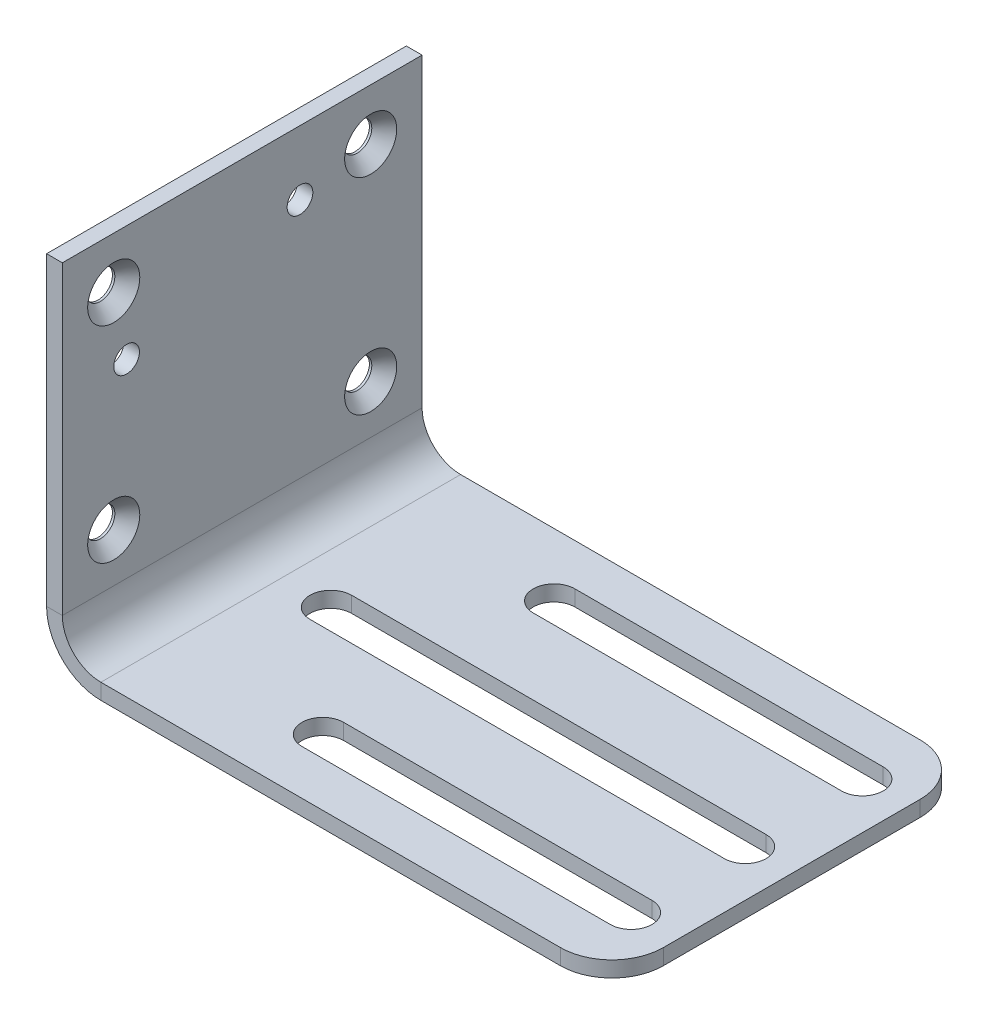
SolidWorks part; units mm, degrees
note: The reader was unsure of these and kept them because the rebuilt part matched: bend radius of "BaseBend1".
material "AISI 1095 CRS, GALV"
ref_plane "Front Plane" through (0, 0, 0) normal (0, 0, 1) x (1, 0, 0)
ref_plane "Top Plane" through (0, 0, 0) normal (0, 1, 0) x (1, 0, 0)
ref_plane "Right Plane" through (0, 0, 0) normal (1, 0, 0) x (0, 0, -1)
sketch "Sketch1" plane through (0, 0, 0) normal (0, 0, 1) x (1, 0, 0)
  line L0 (0, 0) -> (0, 88.9)
  line L1 (0, 0) -> (139.7, 0)
  dimension "D1" = 139.7
  dimension "D2" = 88.9
sheet metal parameters "Sheet-Metal1" thickness 3.8913 parameters "D1"=9.525
base flange "Base-Flange1" sketch "Sketch1" end condition mid plane depth 88.9 reverse direction no thickness 3.8913 reverse thickness direction yes bend radius 9.525
bend "BaseBend1" bend radius 9.525 bend angle 90 parameters "D5"=1
sketch "Sketch4" plane through (0, 3.8913, 0) normal (0, 1, 0) x (1, 0, 0)
  line L0 (25.781, 0) -> (128.1938, 0) construction
  line L1 (25.781, 5.1562) -> (128.1938, 5.1562)
  line L2 (25.781, -5.1562) -> (128.1938, -5.1562)
  line L3 (139.7, -44.45) -> (139.7, 44.45) construction
  line L4 (13.4163, -44.45) -> (139.7, -44.45) construction
  arc A0 (25.781, 5.1562) -> (25.781, -5.1562) centre (25.781, 0) ccw
  arc A1 (128.1938, -5.1562) -> (128.1938, 5.1562) centre (128.1938, 0) ccw
  point P2 (76.9874, 0)
  dimension "D1" = 10.3124
  dimension "D2" = 112.7252
  dimension "D3" = 62.7126
  dimension "D4" = 44.45
extrude "LONG-SLOT" cut sketch "Sketch4" against normal through all normal cut yes
sketch "Sketch5" plane through (0, 3.8913, 0) normal (0, 1, 0) x (1, 0, 0)
  line L0 (51.9938, -28.194) -> (128.1938, -28.194) construction
  line L1 (51.9938, -23.0378) -> (128.1938, -23.0378)
  line L2 (51.9938, -33.3502) -> (128.1938, -33.3502)
  line L3 (13.4163, -44.45) -> (139.7, -44.45) construction
  arc A0 (51.9938, -23.0378) -> (51.9938, -33.3502) centre (51.9938, -28.194) ccw
  arc A1 (128.1938, -33.3502) -> (128.1938, -23.0378) centre (128.1938, -28.194) ccw
  point P2 (90.0938, -28.194)
  dimension "D1" = 10.3124
  dimension "D2" = 86.5124
  dimension "D3" = 16.256
extrude "SHORT-SLOT" cut sketch "Sketch5" against normal through all normal cut yes
pattern_linear "LPattern1" count 2 spacing 57.15 along (0, 0, -1) of "SHORT-SLOT"
hole_wizard "CSK for 1/4 Flat Head Machine Screw1" positions "Sketch7" profile "Sketch6" countersink size "1/4" standard "ANSI Inch" end condition through all
sketch "Sketch7" plane through (3.8913, 0, 0) normal (1, 0, 0) x (0, 0, -1)
  line L0 (-44.45, 88.9) -> (-44.45, 13.4163) construction
  line L1 (-44.45, 88.9) -> (44.45, 88.9) construction
  point P0 (-31.75, 76.2)
  dimension "D1" = 12.7
  dimension "D2" = 12.7
sketch "Sketch6" plane through (3.8913, 76.2, 31.75) normal (0, 1, 0) x (0, 0, -1)
  line L0 (0, 0) -> (0, 3.8913)
  line L1 (0, 3.8913) -> (3.5712, 3.8913)
  line L2 (3.5712, 3.8913) -> (3.5712, 3.2989)
  line L3 (3.5712, 3.2989) -> (6.4389, 0)
  line L5 (6.4389, 0) -> (0, 0)
  line L6 (-3.5712, 3.2989) -> (-6.4389, 0) construction
  line L11 (0, -6.35) -> (0, 107.95) construction
  dimension "Thru Hole Dia." = 7.1425
  dimension "Thru Hole Depth" = 3.8913
  dimension "Near C'Sink Dia." = 12.8778
  dimension "Near C'Sink Angle" = 82
pattern_linear "LPattern2" count 2 spacing 63.5 along (0, 0, -1) count 2 spacing 50.8 along (0, -1, 0) of "CSK for 1/4 Flat Head Machine Screw1"
hole_wizard "1/4 (0.25) Diameter Hole1" positions "Sketch9" profile "Sketch8" hole size "1/4" standard "ANSI Inch" end condition through all
sketch "Sketch9" plane through (3.8913, 0, 0) normal (1, 0, 0) x (0, 0, -1)
  line L0 (-44.45, 88.9) -> (-44.45, 13.4163) construction
  line L1 (-44.45, 88.9) -> (44.45, 88.9) construction
  line L2 (44.45, 88.9) -> (44.45, 13.4163) construction
  point P0 (-28.575, 60.325)
  point P2 (14.2748, 73.025)
  dimension "D1" = 15.875
  dimension "D2" = 28.575
  dimension "D3" = 15.875
  dimension "D4" = 30.1752
sketch "Sketch8" plane through (3.8913, 60.325, 28.575) normal (0, 1, 0) x (0, 0, -1)
  line L0 (0, 0) -> (0, 3.8913)
  line L1 (0, 3.8913) -> (3.175, 3.8913)
  line L2 (3.175, 3.8913) -> (3.175, 0)
  line L5 (3.175, 0) -> (0, 0)
  line L11 (0, -6.35) -> (0, 107.95) construction
  dimension "Thru Hole Dia." = 6.35
  dimension "Thru Hole Depth" = 3.8913
fillet "Fillet1" radius 12.7 2 edges at (139.7, 1.9456, -44.45) (139.7, 1.9456, 44.45)
flat pattern "Flat-Pattern1" [suppressed]
sketch "Bend-Lines1" plane through (0, 3.8913, 0) normal (0, 1, 0) x (1, 0, 0)
  line L0 (4.666, -44.45) -> (4.666, 44.45) construction
  line L1 (4.666, -44.45) -> (4.666, 44.45) construction
sketch3d "Bounding-Box1" [suppressed]
  line L0 (-79.568, 0, 0) -> (139.7, 0, 0) construction
  line L1 (-79.568, 88.9, 0) -> (139.7, 88.9, 0) construction
  line L2 (-79.568, 0, 0) -> (-79.568, 88.9, 0) construction
  line L3 (139.7, 0, 0) -> (139.7, 88.9, 0) construction
bend of the flat pattern "Flatten-<BaseBend1>1"
